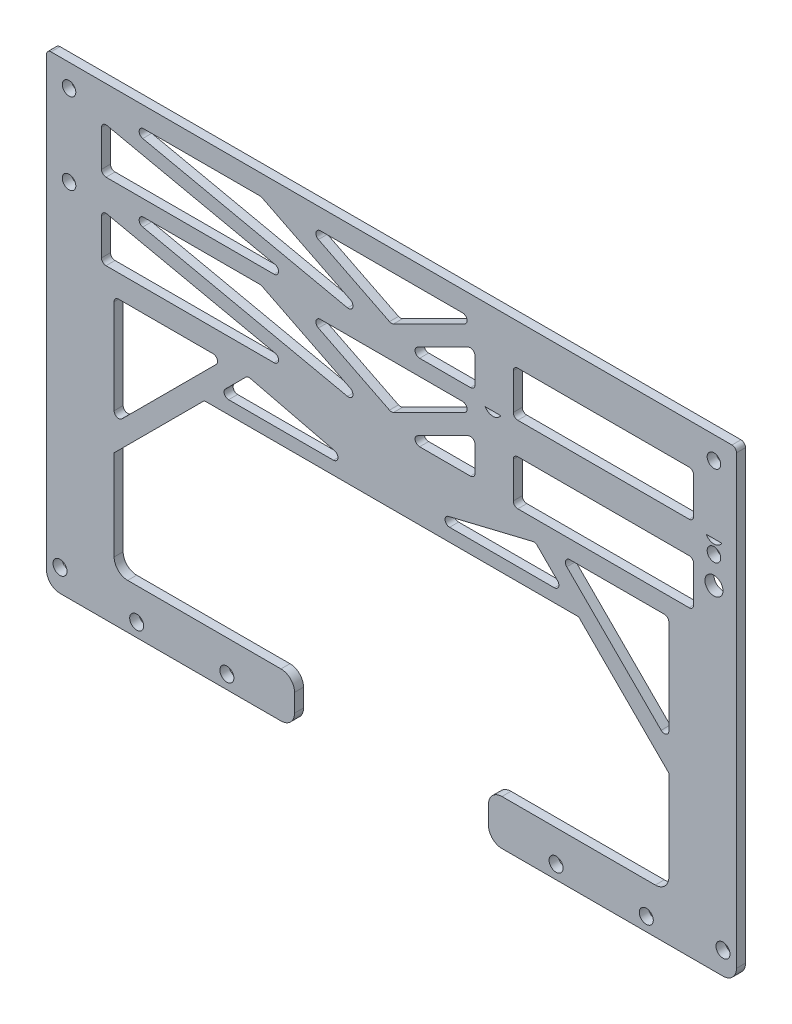
SolidWorks part; units mm, degrees
material "Thornel Mat VMA"
ref_plane "前视基准面" through (0, 0, 0) normal (0, 0, 1) x (1, 0, 0)
ref_plane "上视基准面" through (0, 0, 0) normal (0, 1, 0) x (1, 0, 0)
ref_plane "右视基准面" through (0, 0, 0) normal (1, 0, 0) x (0, 0, -1)
sketch "草图1" plane through (0, 0, 0) normal (0, 0, 1) x (1, 0, 0)
  line L1 (-76.5, 41.5) -> (76.5, 41.5)
  line L2 (-76.5, 41.5) -> (-76.5, -41.5)
  line L3 (-76.5, -41.5) -> (76.5, -41.5)
  line L4 (76.5, 41.5) -> (76.5, -41.5)
  line L5 (-76.5, 41.5) -> (76.5, -41.5) construction
  line L6 (-76.5, -41.5) -> (76.5, 41.5) construction
  point P0 (0, 0)
  dimension "D1" = 153
  dimension "D2" = 83
extrude "凸台-拉伸1" add sketch "草图1" along normal blind 2
sketch "草图2" plane through (0, 0, 2) normal (0, 0, 1) x (1, 0, 0)
  line L0 (-76.5, -41.5) -> (76.5, -41.5) construction
  line L1 (-61.5, -41.5) -> (61.5, -41.5)
  line L2 (-61.5, -41.5) -> (-61.5, 11.5)
  line L3 (-61.5, 11.5) -> (61.5, 11.5)
  line L4 (61.5, -41.5) -> (61.5, 11.5)
  line L5 (-76.5, 41.5) -> (-76.5, -41.5) construction
  line L6 (76.5, 41.5) -> (-76.5, 41.5) construction
  line L7 (76.5, -41.5) -> (76.5, 41.5) construction
  dimension "D1" = 15
  dimension "D2" = 30
  dimension "D3" = 15
extrude "切除-拉伸1" cut sketch "草图2" against normal blind 10
sketch "草图5" plane through (0, 0, 0) normal (0, 0, -1) x (-1, 0, 0)
  circle A0 centre (71.5, 38.5) radius 1.5
extrude "切除-拉伸3" cut sketch "草图5" against normal blind 25
sketch "草图6" plane through (0, 0, -10) normal (0, 0, -1) x (-1, 0, 0)
  circle A0 centre (-71.5, 38.5) radius 1.5
extrude "切除-拉伸4" cut sketch "草图6" against normal blind 25
sketch "草图8" plane through (0, 0, 2) normal (0, 0, 1) x (1, 0, 0)
  circle A0 centre (22.5, 42.5) radius 2
  circle A1 centre (71.5, 42.5) radius 2
  circle A2 centre (71.5, 32.5) radius 2
extrude "切除-拉伸6" cut sketch "草图8" against normal up to next
sketch "草图9" plane through (0, 0, 2) normal (0, 0, 1) x (1, 0, 0)
  line L0 (-76.5, 41.5) -> (-76.5, -41.5) construction
  line L1 (-76.5, -41.5) -> (-61.5, -41.5) construction
  circle A0 centre (-73.5, -36.5) radius 1.55
  dimension "D1" = 3
  dimension "D2" = 5
  dimension "D3" = 3.1
extrude "切除-拉伸7" cut sketch "草图9" against normal blind 10
mirror "镜向1" about plane through (0, 0, 0) normal (1, 0, 0) of "切除-拉伸7"
sketch "草图10" plane through (-61.5, 0, 0) normal (1, 0, 0) x (0, 0, -1)
  line L0 (-2, 11.5) -> (-2, -41.5) construction
  line L1 (0, -41.5) -> (-2, -41.5)
  line L2 (0, -41.5) -> (0, -31.5)
  line L3 (0, -31.5) -> (-2, -31.5)
  line L4 (-2, -41.5) -> (-2, -31.5)
  dimension "D1" = 10
extrude "凸台-拉伸2" add sketch "草图10" along normal blind 40
mirror "镜向2" about plane through (0, 0, 0) normal (1, 0, 0) of "凸台-拉伸2"
sketch "草图11" plane through (0, 0, 2) normal (0, 0, 1) x (1, 0, 0)
  circle A0 centre (-56.5, -38.5) radius 1.55
  circle A1 centre (-36.5, -38.5) radius 1.55
extrude "切除-拉伸8" cut sketch "草图11" against normal blind 3
mirror "镜向3" about plane through (0, 0, 0) normal (1, 0, 0) of "切除-拉伸8"
fillet "圆角1" radius 3 8 edges at (-76.5, -41.5, 1) (61.5, -31.5, 1) (76.5, -41.5, 1) (21.5, -31.5, 1) (21.5, -41.5, 1) (-21.5, -41.5, 1) (-21.5, -31.5, 1) (-61.5, -31.5, 1)
sketch "Sketch2" plane through (0, 0, 0) normal (0, 0, -1) x (-1, 0, 0)
  line L1 (-76.5, 41.5) -> (76.5, 41.5)
  line L2 (-76.5, 41.5) -> (-76.5, 61.5)
  line L3 (-76.5, 61.5) -> (76.5, 61.5)
  line L4 (76.5, 41.5) -> (76.5, 61.5)
  circle A0 centre (71.5, 56.5) radius 1.5
  circle A1 centre (-71.5, 56.5) radius 1.5
  dimension "D2" = 3
  dimension "D3" = 5
  dimension "D4" = 3
  dimension "D1" = 20
extrude "Boss-Extrude1" add sketch "Sketch2" against normal up to surface (2 mm away) up to face at (54.95, -38.5, 2)
pattern_linear "LPattern1" count 4 spacing 10 rebuild error yes
chamfer "Chamfer1" distance 20 angle 45 2 edges at (-61.5, 11.5, 1) (61.5, 11.5, 1)
sketch "Sketch5" plane through (0, 0, 0) normal (0, 0, -1) x (-1, 0, 0)
  line L0 (-20, 57) -> (20, 57)
  line L1 (20, 57) -> (0, 47)
  line L2 (0, 47) -> (-20, 57)
  line L3 (2, 43.5279) -> (28.9443, 57)
  line L4 (28.9443, 57) -> (64.3056, 57)
  line L5 (64.3056, 57) -> (2, 43.5279)
  line L6 (-2, 43.5279) -> (-18.5, 51.7779)
  line L7 (-18.5, 51.7779) -> (-18.5, 43.5279)
  line L8 (-18.5, 43.5279) -> (-2, 43.5279)
  line L9 (16.6887, 43.5279) -> (64.3056, 53.8239)
  line L10 (64.3056, 53.8239) -> (64.3056, 43.5279)
  line L11 (64.3056, 43.5279) -> (16.6887, 43.5279)
  line L13 (-71.5, 52.5) -> (-22.5, 42.5) construction
  line L15 (-67, 42.5) -> (-27, 42.5)
  line L16 (-67, 42.5) -> (-67, 52.5)
  line L17 (-67, 52.5) -> (-27, 52.5)
  line L18 (-27, 42.5) -> (-27, 52.5)
  line L19 (-67, 42.5) -> (-27, 52.5) construction
  line L20 (-67, 52.5) -> (-27, 42.5) construction
  circle A0 centre (-22.5, 42.5) radius 2 construction
  point P9 (-47, 47.5)
  dimension "D1" = 47
  dimension "D2" = 40
  dimension "D3" = 20
  dimension "D4" = 10
  dimension "D5" = 4
  dimension "D6" = 0
  dimension "D7" = 2
  dimension "D8" = 4
  dimension "D9" = 4
  dimension "D10" = 0
  dimension "D11" = 10
  dimension "D12" = 40
extrude "Cut-Extrude1" cut sketch "Sketch5" against normal blind 10
fillet "Fillet1" radius 1 16 edges at (67, 42.5, 1) (67, 52.5, 1) (27, 42.5, 1) (27, 52.5, 1) (-28.9443, 57, 1) (-64.3056, 53.8239, 1) (-64.3056, 57, 1) (18.5, 51.7779, 1) (-2, 43.5279, 1) (-16.6887, 43.5279, 1) (18.5, 43.5279, 1) (-64.3056, 43.5279, 1) (2, 43.5279, 1) (-20, 57, 1) (0, 47, 1) (20, 57, 1)
pattern_linear "LPattern2" count 2 spacing 17 along (0, -1, 0) of "Cut-Extrude1", "Fillet1"
sketch "Sketch6" plane through (0, 0, 0) normal (0, 0, -1) x (-1, 0, 0)
  line L0 (37.1569, 21.5) -> (61.5, -2.8431)
  line L1 (61.5, -2.8431) -> (61.5, 21.5)
  line L2 (61.5, 21.5) -> (37.1569, 21.5)
  line L3 (41.5, 11.5) -> (61.5, -8.5) construction
  line L4 (-41.5, 11.5) -> (41.5, 11.5) construction
  line L5 (61.5, -8.5) -> (61.5, -28.5) construction
  dimension "D1" = 4
  dimension "D2" = 10
  dimension "D3" = 0
extrude "Cut-Extrude2" cut sketch "Sketch6" against normal blind 10
fillet "Fillet2" radius 1 3 edges at (-61.5, -2.8431, 1) (-37.1569, 21.5, 1) (-61.5, 21.5, 1)
mirror "Mirror1" about plane through (0, 0, 0) normal (1, 0, 0) of "Fillet2", "Cut-Extrude2"
fillet "Fillet3" radius 1 2 edges at (76.5, 61.5, 1) (-76.5, 61.5, 1)
sketch "Sketch7" plane through (0, 0, 0) normal (0, 0, -1) x (-1, 0, 0)
  line L0 (-38.5315, 14.3896) -> (-31.8937, 21.0273)
  line L1 (-31.8937, 21.0273) -> (-4.5017, 14.3896)
  line L2 (-4.5017, 14.3896) -> (-38.5315, 14.3896)
extrude "Cut-Extrude3" cut sketch "Sketch7" against normal blind 10
fillet "Fillet4" radius 1 3 edges at (4.5017, 14.3896, 1) (31.8937, 21.0273, 1) (38.5315, 14.3896, 1)
mirror "Mirror2" about plane through (0, 0, 0) normal (1, 0, 0) of "Cut-Extrude3", "Fillet4"
